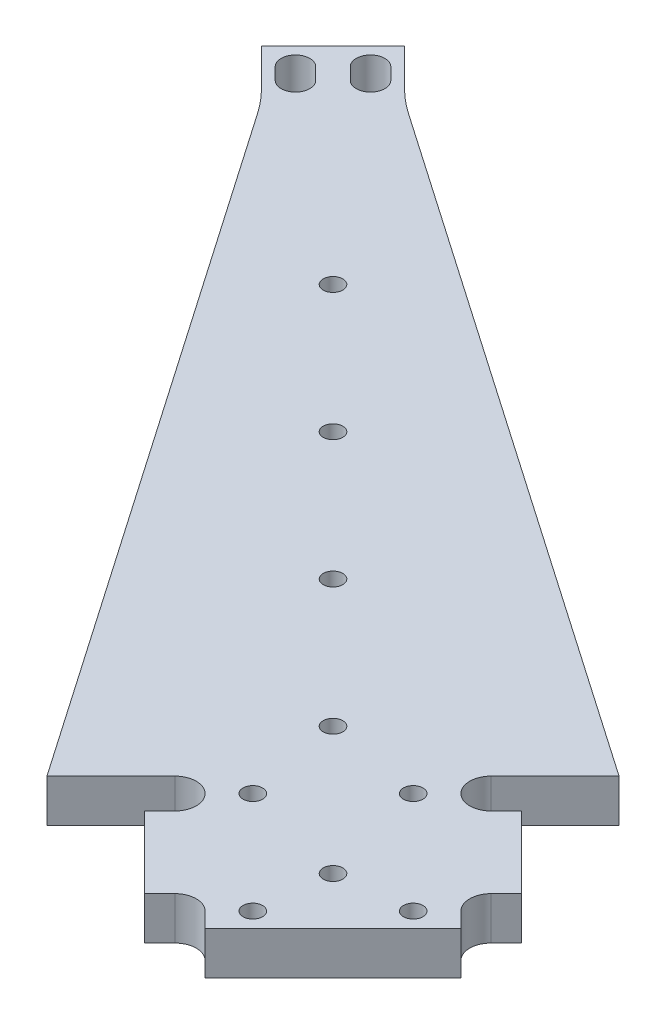
SolidWorks part; units mm, degrees
material "6061 Alloy"
ref_plane "Front Plane" through (0, 0, 0) normal (0, 0, 1) x (1, 0, 0)
ref_plane "Top Plane" through (0, 0, 0) normal (0, 1, 0) x (1, 0, 0)
ref_plane "Right Plane" through (0, 0, 0) normal (1, 0, 0) x (0, 0, -1)
sketch "Sketch11" plane through (0, 0, 0) normal (0, -1, 0) x (1, 0, 0)
  circle A3 centre (14.0092, 8.4414) radius 2.286
  circle A7 centre (8.4414, 14.0092) radius 2.286
sketch "Sketch1" plane through (0, 0, 0) normal (0, 1, 0) x (1, 0, 0)
  line L0 (0, -99) -> (0, 99) construction
  line L1 (-99, 0) -> (99, 0) construction
  line L2 (-98.7155, -7.5) -> (98.7155, -7.5) construction
  line L3 (7.5, -98.7155) -> (7.5, 98.7155) construction
  line L4 (-98.7155, 7.5) -> (98.7155, 7.5) construction
  line L5 (-7.5, -98.7155) -> (-7.5, 98.7155) construction
  line L6 (-7.5, -99) -> (-7.5, 99) construction
  line L7 (7.5, -99) -> (7.5, 99) construction
  line L8 (-99, -7.5) -> (99, -7.5) construction
  line L9 (-99, 7.5) -> (99, 7.5) construction
  line L10 (-88.3883, -88.3883) -> (17.6777, -194.4544) construction
  line L11 (17.6777, -194.4544) -> (194.4544, -17.6777) construction
  line L12 (194.4544, -17.6777) -> (88.3883, 88.3883) construction
  line L13 (-1.5531, -1.5531) -> (33754.4226, 33754.4226) construction
  line L14 (-88.3883, -88.3883) -> (-70.0036, -70.0036) construction
  line L15 (88.3883, 88.3883) -> (70.0036, 70.0036) construction
  line L16 (106.066, -106.066) -> (70.0036, -70.0036) construction
  line L17 (80.2566, -122.683) -> (9.4576, -20.0642)
  line L18 (9.4576, -20.0642) -> (2.3865, -12.9931)
  line L19 (91.9858, -110.9539) -> (96.4759, -115.444)
  line L20 (2.3865, -12.9931) -> (12.9931, -2.3865)
  line L21 (96.4759, -115.444) -> (91.9858, -119.9341)
  line L22 (12.9931, -2.3865) -> (20.0642, -9.4576)
  line L23 (110.6622, -101.4698) -> (74.4487, -65.2563) construction
  line L24 (88.3883, 79.196) -> (74.4487, 65.2563) construction
  line L25 (185.262, -17.6777) -> (88.3883, 79.196) construction
  line L26 (17.6777, -185.262) -> (185.262, -17.6777) construction
  line L27 (-79.196, -88.3883) -> (17.6777, -185.262) construction
  line L28 (-79.196, -88.3883) -> (-65.2563, -74.4487) construction
  line L29 (20.0642, -9.4576) -> (122.683, -80.2566)
  line L30 (-79.196, -88.3883) -> (-65.4074, -74.5998) construction
  line L31 (91.9858, -119.9341) -> (102.5924, -130.5408)
  line L32 (88.3883, 79.196) -> (74.5998, 65.4074) construction
  line L33 (102.5924, -130.5408) -> (107.0825, -126.0506)
  line L34 (110.6622, -101.4698) -> (74.5998, -65.4074) construction
  line L35 (0, 0) -> (101.4698, -101.4698) construction
  line L38 (-14.9371, -14.9371) -> (7.0711, 7.0711) construction
  line L39 (80.2566, -122.683) -> (122.683, -80.2566)
  line L40 (107.0825, -126.0506) -> (111.5726, -130.5408)
  line L41 (111.5726, -130.5408) -> (130.5408, -111.5726)
  line L42 (130.5408, -111.5726) -> (126.0506, -107.0825)
  line L43 (126.0506, -107.0825) -> (130.5408, -102.5924)
  line L44 (130.5408, -102.5924) -> (119.9341, -91.9858)
  line L45 (119.9341, -91.9858) -> (115.444, -96.4759)
  line L46 (115.444, -96.4759) -> (110.9539, -91.9858)
  line L47 (7.5576, -13.1253) -> (9.3253, -14.8931) construction
  line L48 (9.0602, -11.6227) -> (10.8279, -13.3905)
  line L49 (6.055, -14.6279) -> (7.8227, -16.3957)
  line L50 (13.1253, -7.5576) -> (14.8931, -9.3253) construction
  line L51 (11.6227, -9.0602) -> (13.3905, -10.8279)
  line L52 (14.6279, -6.055) -> (16.3957, -7.8227)
  circle A0 centre (0, 0) radius 100 construction
  circle A1 centre (0, 0) radius 99 construction
  circle A2 centre (0, 0) radius 84 construction
  arc A3 (9.0602, -11.6227) -> (6.055, -14.6279) centre (7.5576, -13.1253) ccw
  arc A4 (7.8227, -16.3957) -> (10.8279, -13.3905) centre (9.3253, -14.8931) ccw
  circle A5 centre (8.4414, -14.0092) radius 2.25 construction
  circle A6 centre (14.0092, -8.4414) radius 2.25 construction
  arc A7 (11.6227, -9.0602) -> (14.6279, -6.055) centre (13.1253, -7.5576) cw
  arc A8 (16.3957, -7.8227) -> (13.3905, -10.8279) centre (14.8931, -9.3253) cw
  point P0 (101.4698, -101.4698)
  point P7 (0, 0)
  point P11 (0, 0)
  point P43 (7.6898, -7.6898)
  point P77 (8.4414, -14.0092)
  point P86 (14.0092, -8.4414)
  dimension "D1" = 200
  dimension "D2" = 1
  dimension "D3" = 15
  dimension "D6" = 25
  dimension "D7" = 25
  dimension "D8" = 50
  dimension "D11" = 4.5
  dimension "D9" = 7.5
  dimension "D10" = 45
  dimension "D15" = 60
  dimension "D12" = 143.5
  dimension "D13" = 10
  dimension "D14" = 15
  dimension "D16" = 5
  dimension "D17" = 6.35
  dimension "D18" = 15
  dimension "D19" = 6.35
  dimension "D20" = 26.825
  dimension "D21" = 16.5875
  dimension "D22" = 6.35
  dimension "D23" = 4.25
  dimension "D24" = 2.5
  dimension "D4" = 7.5
  dimension "D5" = 7.5
extrude "Boss-Extrude1" add sketch "Sketch1" along normal mid plane 6.35
hole_wizard "#8-32 Tapped Hole1" [suppressed] positions "Sketch7" profile "Sketch8" tap size "#8-32" standard "ANSI Inch"
sketch "Sketch7" plane through (101.4698, 0, 101.4698) normal (0.7071, 0, 0.7071) x (0.7071, 0, -0.7071)
  point P0 (20, 0)
  point P2 (-20, 0)
  dimension "D1" = 20
  dimension "D2" = 20
sketch "Sketch8" plane through (115.612, 0, 87.3277) normal (0, 1, 0) x (0.7071, 0, -0.7071)
  line L0 (0, 0) -> (0, 11.7478)
  line L1 (0, 11.7478) -> (1.7272, 10.71)
  line L2 (1.7272, 10.71) -> (1.7272, 0)
  line L5 (1.7272, 0) -> (0, 0)
  line L10 (0, 11.7478) -> (-1.7272, 10.71) construction
  line L11 (0, -6.35) -> (0, 107.95) construction
  dimension "Tap Drill Dia." = 3.4544
  dimension "Tap Drill Depth" = 10.71
  dimension "Drill Angle" = 118
cosmetic thread "Hole Thread1" [suppressed] parameters "D1"=8.33, "D2"=4.1656
cosmetic thread "Hole Thread2" [suppressed] parameters "D1"=8.33, "D2"=4.1656
hole_wizard "3/16 (0.1875) Dowel Hole1" [suppressed] positions "Sketch9" profile "Sketch10" hole size "3/16" standard "ANSI Inch"
sketch "Sketch9" plane through (101.4698, 0, 101.4698) normal (0.7071, 0, 0.7071) x (0.7071, 0, -0.7071)
  point P0 (-10, 0)
  point P2 (10, 0)
  dimension "D1" = 10
  dimension "D2" = 10
sketch "Sketch10" plane through (94.3988, 0, 108.5409) normal (0, 1, 0) x (0.7071, 0, -0.7071)
  line L0 (0, 0) -> (0, 14.2608)
  line L1 (0, 14.2608) -> (2.3812, 12.83)
  line L2 (2.3812, 12.83) -> (2.3812, 0)
  line L5 (2.3812, 0) -> (0, 0)
  line L10 (0, 14.2608) -> (-2.3813, 12.83) construction
  line L11 (0, -6.35) -> (0, 107.95) construction
  dimension "Hole Dia." = 4.7625
  dimension "Hole Depth" = 12.83
  dimension "Drill Angle" = 118
fillet "Fillet1" radius 25 2 edges at (20.0642, 0, 9.4576) (9.4576, 0, 20.0642)
hole_wizard "M2.5 Clearance Hole1" positions "Sketch12" profile "Sketch13" hole size "M2.5" standard "ANSI Metric" end condition up to next
sketch "Sketch12" plane through (0, 3.175, 0) normal (0, 1, 0) x (1, 0, 0)
  line L0 (97.7664, -109.6634) -> (112.8631, -124.7602)
  line L1 (97.7664, -109.6634) -> (109.6634, -97.7664)
  line L2 (112.8631, -124.7602) -> (124.7602, -112.8631)
  line L3 (109.6634, -97.7664) -> (124.7602, -112.8631)
  line L4 (111.5726, -130.5408) -> (130.5408, -111.5726) construction
  line L6 (91.9858, -110.9539) -> (96.4759, -115.444) construction
  line L7 (113.9856, -113.9856) -> (95.0705, -95.0705)
  line L8 (95.0705, -95.0705) -> (76.1554, -76.1554)
  line L9 (76.1554, -76.1554) -> (57.2403, -57.2403)
  line L10 (57.2403, -57.2403) -> (38.3252, -38.3252)
  line L12 (121.0567, -121.0567) -> (113.9856, -113.9856)
  point P0 (97.7664, -109.6634)
  point P2 (109.6634, -97.7664)
  point P4 (112.8631, -124.7602)
  point P6 (124.7602, -112.8631)
  point P148 (38.3252, -38.3252)
  point P151 (57.2403, -57.2403)
  point P154 (76.1554, -76.1554)
  point P157 (95.0705, -95.0705)
  point P160 (113.9856, -113.9856)
  dimension "D1" = 16.825
  dimension "D2" = 3.175
  dimension "D3" = 21.35
  dimension "D4" = 5
  dimension "D5" = 10
  dimension "D6" = 26.75
sketch "Sketch13" plane through (97.7664, 3.175, 109.6634) normal (1, 0, 0) x (0, 0, 1)
  line L0 (0, 0) -> (0, 6.35)
  line L1 (0, 6.35) -> (1.45, 6.35)
  line L2 (1.45, 6.35) -> (1.45, 0)
  line L5 (1.45, 0) -> (0, 0)
  line L11 (0, -6.35) -> (0, 107.95) construction
  dimension "Thru Hole Dia." = 2.9
  dimension "Thru Hole Depth" = 6.35
fillet "Fillet2" radius 3.175 6 edges at (110.9539, 0, 91.9858) (115.444, 0, 96.4759) (126.0506, 0, 107.0825) (107.0825, 0, 126.0506) (96.4759, 0, 115.444) (91.9858, 0, 110.9539)
